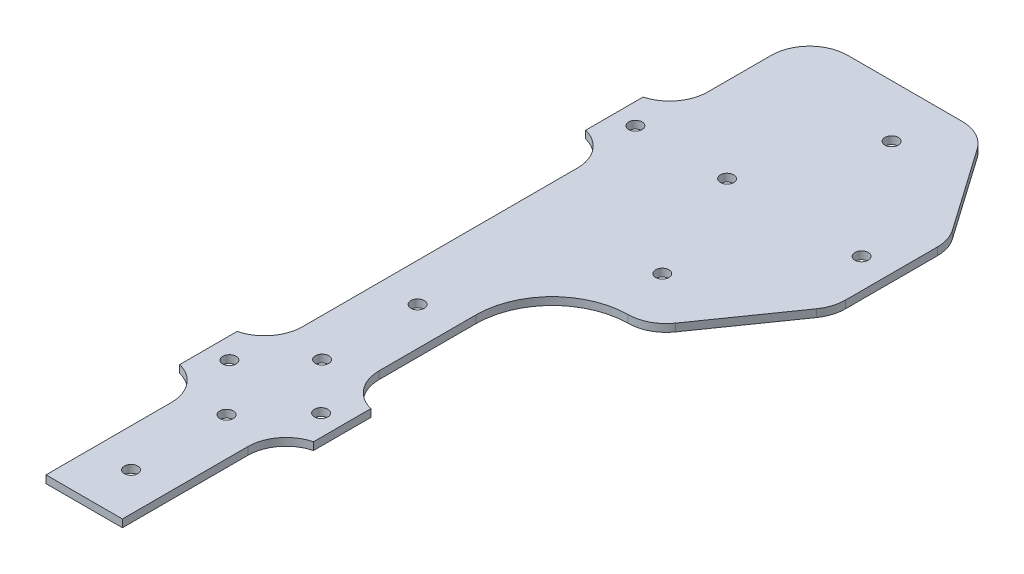
SolidWorks part; units mm, degrees
ref_plane "Piano frontale" through (0, 0, 0) normal (0, 0, 1) x (1, 0, 0)
ref_plane "Piano superiore" through (0, 0, 0) normal (0, 1, 0) x (1, 0, 0)
ref_plane "Piano destro" through (0, 0, 0) normal (1, 0, 0) x (0, 0, -1)
sketch "Schizzo1" plane through (0, 0, 0) normal (0, 1, 0) x (1, 0, 0)
  line L1 (-10, -100) -> (10, -100)
  line L2 (-10, -100) -> (-10, -57.5)
  line L3 (-10, 100) -> (10, 100)
  line L4 (10, -100) -> (10, -57.5)
  line L5 (-10, -100) -> (10, 100) construction
  line L6 (-10, 100) -> (10, -100) construction
  line L7 (-17.5, -57.5) -> (-10, -57.5)
  line L8 (-17.5, -57.5) -> (-17.5, -42.5)
  line L9 (-17.5, -42.5) -> (-10, -42.5)
  line L10 (17.5, -57.5) -> (17.5, -42.5)
  line L11 (-17.5, -57.5) -> (17.5, -42.5) construction
  line L12 (-17.5, -42.5) -> (17.5, -57.5) construction
  line L16 (-10, -42.5) -> (-10, 12.5)
  line L17 (10, -57.5) -> (17.5, -57.5)
  line L18 (10, -42.5) -> (10, 12.5)
  line L19 (10, -42.5) -> (17.5, -42.5)
  line L20 (10, 12.5) -> (55, 12.5)
  line L21 (-30, 100) -> (55, 100)
  line L22 (-30, 100) -> (-30, 12.5)
  line L23 (-30, 12.5) -> (-10, 12.5)
  line L24 (55, 100) -> (55, 12.5)
  line L25 (-12, 56.25) -> (12, 56.25) construction
  line L26 (0, -100) -> (0, 100) construction
  line L27 (25.04, 69.5) -> (25.04, -49930.5) construction
  circle A0 centre (0, -87.75) radius 1.75
  circle A1 centre (0, -62.75) radius 1.75
  circle A2 centre (0, -37.75) radius 1.75
  circle A3 centre (0, -12.75) radius 1.75
  circle A4 centre (-12, -50) radius 1.75
  circle A5 centre (12, -50) radius 1.75
  circle A6 centre (-12, 56.25) radius 1.75
  circle A7 centre (12, 56.25) radius 1.75
  circle A8 centre (25.04, 86.25) radius 1.75
  circle A9 centre (47.2, 56.25) radius 1.75
  circle A10 centre (25.04, 26.25) radius 1.75
  point P0 (0, 0)
  point P7 (0, -50)
  point P43 (0, -100)
  dimension "D6" = 3.5
  dimension "D10" = 3.5
  dimension "D9" = 3.5
  dimension "D16" = 3.5
  dimension "D17" = 3.5
  dimension "D18" = 3.5
  dimension "D1" = 200
  dimension "D2" = 20
  dimension "D3" = 35
  dimension "D4" = 15
  dimension "D5" = 50
  dimension "D7" = 12.25
  dimension "D11" = 24
  dimension "D12" = 85
  dimension "D13" = 87.5
  dimension "D14" = 20
  dimension "D19" = 30
  dimension "D20" = 43.75
  dimension "D21" = 77.2
  dimension "D22" = 50
  dimension "D23" = 22.16
  dimension "D24" = 60
  dimension "D25" = 25
  dimension "D26" = 12
  dimension "D27" = 20
  dimension "D28" = 10
  dimension "D8" = 4
  dimension "D15" = 2
extrude "Estrusione-Estrusione1" add sketch "Schizzo1" against normal blind 2 contours L24 L21 L3 L22 L23 L16 L9 L8 L7 L2 L1 L4 L17 L10 L19 L18 L20 A10 A9 A8 A7 A6 A5 A4 A3 A2 A1 A0 region at (9.3847, 0, -31.4951)
chamfer "Smusso1" distance 20 angle 55 2 edges at (55, -1, -100) (55, -1, -12.5) first distance on face at (12.5, -1, -100) first distance on face at (32.5, -1, -12.5)
sketch "Schizzo2" plane through (0, 0, 0) normal (0, 1, 0) x (1, 0, 0)
  line L0 (-10, 12.5) -> (-10, 48.75)
  line L1 (-10, 48.75) -> (-17.5, 48.75)
  line L2 (-17.5, 48.75) -> (-17.5, 63.75)
  line L3 (-17.5, 63.75) -> (-10.1785, 63.75)
  line L4 (-10.1785, 63.75) -> (-10.1785, 100)
  line L5 (-30, 100) -> (35, 100) construction
  line L6 (-10.1785, 100) -> (-33.8092, 100)
  line L7 (-33.8092, 100) -> (-33.8092, 12.5)
  line L8 (-33.8092, 12.5) -> (-10, 12.5)
  line L9 (-17.5, 56.25) -> (-0.7692, 56.25) construction
  line L10 (-17.5, 66.25) -> (-17.5, 33.3718) construction
  line L11 (-17.5, -57.5) -> (-17.5, -42.5) construction
  point P13 (-12, 56.25)
  dimension "D1" = 15
extrude "Taglio-Estrusione1" cut sketch "Schizzo2" against normal blind 10
fillet "Raccordo1" radius 10 11 edges at (10, -1, 42.5) (-10, -1, 42.5) (-10, -1, 57.5) (10, -1, 57.5) (35, -1, -12.5) (55, -1, -41.063) (35, -1, -100) (55, -1, -71.437) (-10.1785, -1, -100) (-10.1785, -1, -63.75) (-10, -1, -48.75)
fillet "Raccordo2" radius 20 1 edges at (10, -1, -12.5)
